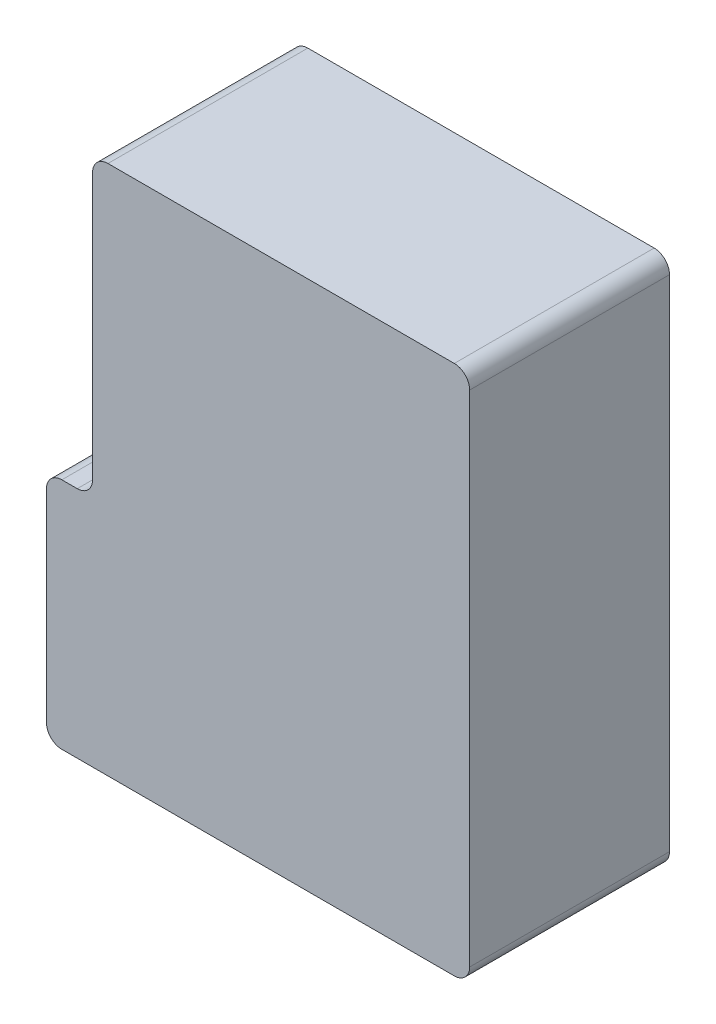
SolidWorks part; units mm, degrees
material "Custom Plastic"
ref_plane "X-Y Datum" through (0, 0, 0) normal (0, 0, 1) x (1, 0, 0)
ref_plane "X-Z Datum" through (0, 0, 0) normal (0, 1, 0) x (1, 0, 0)
ref_plane "Y-Z Datum" through (0, 0, 0) normal (1, 0, 0) x (0, 0, -1)
sketch "Sketch1" plane through (0, 0, 0) normal (0, 0, 1) x (1, 0, 0)
  line L0 (1.8162, 48.1563) -> (125.4513, 48.1563) construction
  line L1 (24.3593, 48.1563) -> (24.3593, 120.2923) construction
  line L3 (24.3593, 120.2923) -> (125.4513, 120.2923) construction
  line L8 (125.4513, 48.1563) -> (125.4513, 120.2923) construction
  line L33 (24.3593, 120.2923) -> (1.8162, 120.2923) construction
  line L34 (24.3593, 120.2923) -> (24.3593, 48.1563) construction
  line L35 (63.6337, 48.1563) -> (63.6337, 43.0763) construction
  line L36 (1.8162, 120.2923) -> (1.8162, 48.1563) construction
  line L41 (24.3593, 120.2923) -> (23.7243, 120.2923) construction
  line L42 (24.3593, 120.2923) -> (24.3593, 122.8323) construction
  line L44 (27.5343, 14.7553) -> (27.5343, 43.0763) construction
  line L45 (125.4513, 120.2923) -> (127.9913, 120.2923) construction
  line L46 (27.5343, 14.7553) -> (125.4513, 14.7553) construction
  line L47 (23.7243, 122.8323) -> (127.9913, 122.8323)
  line L48 (23.7243, 122.8323) -> (23.7243, -21.9477)
  line L49 (23.7243, -21.9477) -> (127.9913, -21.9477)
  line L50 (127.9913, 122.8323) -> (127.9913, -21.9477)
  line L51 (125.4513, 14.7553) -> (125.4513, 43.0763) construction
  line L52 (27.5343, 43.0763) -> (125.4513, 43.0763) construction
  line L53 (23.7243, 120.2923) -> (23.7243, 48.1563) construction
  circle A17 centre (30.4553, 114.1963) radius 2.1 construction
  circle A18 centre (119.8633, 115.2123) radius 2.1 construction
  circle A19 centre (119.6813, 54.2533) radius 2.1 construction
  circle A20 centre (29.4393, 53.2363) radius 2.1 construction
  circle A26 centre (31.9793, 18.4383) radius 2.1 construction
  circle A27 centre (31.9793, 39.3933) radius 2.1 construction
  circle A28 centre (120.6193, 28.8183) radius 2.1 construction
sketch "Sketch2" plane through (0, 0, 0) normal (0, 0, 1) x (1, 0, 0)
  line L4 (55.176, 122.8323) -> (127.9913, 122.8323)
  line L6 (55.176, 48.5244) -> (55.176, 50.9244) construction
  line L7 (55.176, -21.05) -> (127.9913, -21.05)
  line L8 (127.9913, 122.8323) -> (127.9913, -21.05)
  line L9 (55.176, 110.2103) -> (127.9913, -21.05) construction
  line L10 (55.176, -8.428) -> (127.9913, 122.8323) construction
  line L11 (55.176, 50.9244) -> (55.176, -21.05)
  line L12 (55.176, 50.9244) -> (55.176, 122.8323)
  circle A7 centre (88.0827, 6.45) radius 27.5
  circle A8 centre (88.0294, 95.3501) radius 27.5
  circle A9 centre (98.216, 50.8911) radius 6.477
  circle A10 centre (77.896, 50.9089) radius 6.477
  circle A11 centre (121.5143, 31.8208) radius 6.477
  circle A12 centre (115.996, 50.8756) radius 2.4
  circle A13 centre (55.176, 50.9244) radius 2.4
  point P14 (88.0827, 50.8911)
sketch "Sketch3" plane through (0, 0, 0) normal (0, 0, 1) x (1, 0, 0)
  line L0 (119.5956, 120.2923) -> (119.5956, 122.8323) construction
  line L1 (24.3593, 120.2923) -> (125.4513, 120.2923) construction
  line L2 (127.9913, 122.8323) -> (127.9913, 110.1323) construction
  line L3 (127.9913, 122.8323) -> (127.9913, -21.9477) construction
  line L4 (127.9913, 110.1323) -> (130.5313, 110.1323) construction
  line L5 (127.9913, -21.9477) -> (127.9913, -9.2477) construction
  line L6 (127.9913, -9.2477) -> (130.5313, -9.2477) construction
  line L7 (127.9913, 50.4423) -> (130.5313, 50.4423) construction
  line L8 (75.8578, 122.8323) -> (75.8578, -32.9894) construction
  line L9 (23.7243, 122.8323) -> (127.9913, 122.8323) construction
  line L10 (23.7243, 31.0503) -> (21.1843, 31.0503) construction
  line L11 (23.7243, -9.2477) -> (21.1843, -9.2477) construction
  line L12 (23.7243, -21.9477) -> (23.7243, -9.2477) construction
  line L13 (23.7243, 122.8323) -> (23.7243, -21.9477) construction
  line L14 (23.7243, 122.8323) -> (23.7243, 110.1323) construction
  line L15 (32.12, 120.2923) -> (32.12, 122.8323) construction
  line L17 (23.7243, 135.5323) -> (143.2313, 135.5323)
  line L18 (8.4843, 37.4003) -> (8.4843, -34.6477)
  line L19 (8.4843, -34.6477) -> (143.2313, -34.6477)
  line L20 (143.2313, 135.5323) -> (143.2313, -34.6477)
  line L22 (23.7243, 48.1563) -> (23.7243, 135.5323)
  line L23 (8.4843, 37.4003) -> (23.7243, 37.4003)
  line L24 (23.7243, 37.4003) -> (23.7243, 48.1563)
  circle A0 centre (119.5956, 129.1823) radius 6.35 construction
  circle A1 centre (136.8813, 110.1323) radius 6.35 construction
  circle A2 centre (136.8813, -9.2477) radius 6.35 construction
  circle A3 centre (136.8813, 50.4423) radius 6.35 construction
  circle A4 centre (119.5956, -28.2977) radius 6.35 construction
  circle A5 centre (32.12, -28.2977) radius 6.35 construction
  circle A7 centre (14.8343, -9.2477) radius 6.35 construction
  circle A9 centre (32.12, 129.1823) radius 6.35 construction
  circle A10 centre (14.8343, 31.0503) radius 6.35 construction
extrude "Boss-Extrude1" add sketch "Sketch3" along normal blind 63.5
shell "Shell1" thickness 2.54 removed face at (58.48, 46.095, 0) outward yes
sketch "Sketch6" plane through (0, 0, 63.5) normal (0, 0, -1) x (-1, 0, 0)
  line L0 (-125.9456, -28.2977) -> (-125.9456, -34.6477)
  line L1 (-8.4843, -34.6477) -> (-143.2313, -34.6477) construction
  line L2 (-125.9456, -34.6477) -> (-113.2456, -34.6477)
  line L3 (-113.2456, -34.6477) -> (-113.2456, -28.2977)
  line L4 (-136.8813, -2.8977) -> (-143.2313, -2.8977)
  line L5 (-143.2313, 135.5323) -> (-143.2313, -34.6477) construction
  line L6 (-143.2313, -2.8977) -> (-143.2313, -15.5977)
  line L7 (-143.2313, -15.5977) -> (-136.8813, -15.5977)
  line L8 (-38.47, -28.2977) -> (-38.47, -34.6477)
  line L9 (-38.47, -34.6477) -> (-25.77, -34.6477)
  line L10 (-25.77, -34.6477) -> (-25.77, -28.2977)
  line L11 (-14.8343, -2.8977) -> (-8.4843, -2.8977)
  line L12 (-8.4843, 37.4003) -> (-8.4843, -34.6477) construction
  line L13 (-8.4843, -2.8977) -> (-8.4843, -15.5977)
  line L14 (-8.4843, -15.5977) -> (-14.8343, -15.5977)
  line L15 (-14.8343, 24.7003) -> (-8.4843, 24.7003)
  line L16 (-8.4843, 24.7003) -> (-8.4843, 37.4003)
  line L17 (-8.4843, 37.4003) -> (-14.8343, 37.4003)
  line L18 (-136.8813, 56.7923) -> (-143.2313, 56.7923)
  line L19 (-143.2313, 56.7923) -> (-143.2313, 44.0923)
  line L20 (-143.2313, 44.0923) -> (-136.8813, 44.0923)
  line L21 (-136.8813, 116.4823) -> (-143.2313, 116.4823)
  line L22 (-143.2313, 116.4823) -> (-143.2313, 103.7823)
  line L23 (-143.2313, 103.7823) -> (-136.8813, 103.7823)
  line L24 (-125.9456, 129.1823) -> (-125.9456, 135.5323)
  line L25 (-23.7243, 135.5323) -> (-143.2313, 135.5323) construction
  line L26 (-125.9456, 135.5323) -> (-113.2456, 135.5323)
  line L27 (-113.2456, 135.5323) -> (-113.2456, 129.1823)
  line L28 (-38.47, 129.1823) -> (-38.47, 135.5323)
  line L29 (-25.77, 129.1823) -> (-23.7243, 129.1823)
  line L30 (-23.7243, 48.1563) -> (-23.7243, 135.5323) construction
  line L31 (-23.7243, 129.1823) -> (-23.7243, 135.5323)
  line L32 (-23.7243, 135.5323) -> (-38.47, 135.5323)
  line L33 (-75.8578, 122.8323) -> (-75.8578, -32.9894) construction
  line L34 (-82.2078, 129.1823) -> (-82.2078, 135.5323)
  line L35 (-82.2078, 135.5323) -> (-69.5078, 135.5323)
  line L36 (-69.5078, 135.5323) -> (-69.5078, 129.1823)
  line L37 (-82.2078, -28.2977) -> (-82.2078, -34.6477)
  line L38 (-82.2078, -34.6477) -> (-69.5078, -34.6477)
  line L39 (-69.5078, -34.6477) -> (-69.5078, -28.2977)
  arc A0 (-125.9456, 129.1823) -> (-113.2456, 129.1823) centre (-119.5956, 129.1823) ccw
  arc A1 (-38.47, 129.1823) -> (-25.77, 129.1823) centre (-32.12, 129.1823) ccw
  arc A2 (-136.8813, 103.7823) -> (-136.8813, 116.4823) centre (-136.8813, 110.1323) ccw
  arc A3 (-136.8813, 44.0923) -> (-136.8813, 56.7923) centre (-136.8813, 50.4423) ccw
  arc A4 (-136.8813, -15.5977) -> (-136.8813, -2.8977) centre (-136.8813, -9.2477) ccw
  arc A5 (-113.2456, -28.2977) -> (-125.9456, -28.2977) centre (-119.5956, -28.2977) ccw
  arc A6 (-14.8343, -2.8977) -> (-14.8343, -15.5977) centre (-14.8343, -9.2477) ccw
  arc A7 (-14.8343, 37.4003) -> (-14.8343, 24.7003) centre (-14.8343, 31.0503) ccw
  arc A8 (-25.77, -28.2977) -> (-38.47, -28.2977) centre (-32.12, -28.2977) ccw
  arc A9 (-69.5078, -28.2977) -> (-82.2078, -28.2977) centre (-75.8578, -28.2977) ccw
  arc A10 (-82.2078, 129.1823) -> (-69.5078, 129.1823) centre (-75.8578, 129.1823) ccw
extrude "Boss-Extrude2" add sketch "Sketch6" along normal blind 63.5
sketch "Sketch7" plane through (0, 0, 63.5) normal (0, 0, -1) x (-1, 0, 0)
  line L0 (-23.7243, 58.6553) -> (-23.7243, 46.8863) construction
  line L1 (-27.7674, 119.0223) -> (-128.8594, 119.0223) construction
  line L2 (-27.7674, 119.0223) -> (-27.7674, 46.8863) construction
  line L3 (-27.7674, 46.8863) -> (-128.8594, 46.8863) construction
  line L4 (-128.8594, 119.0223) -> (-128.8594, 46.8863) construction
  line L5 (-27.7674, 46.8863) -> (-5.2243, 46.8863) construction
  line L6 (-27.7674, 46.8863) -> (-27.7674, 119.0223) construction
  line L7 (-27.7674, 119.0223) -> (-5.2243, 119.0223) construction
  line L8 (-5.2243, 46.8863) -> (-5.2243, 119.0223) construction
  circle A0 centre (-123.0894, 112.9253) radius 6.35
  circle A1 centre (-32.8474, 113.9423) radius 6.35
  circle A2 centre (-120.6193, 28.8183) radius 6.35
  circle A3 centre (-31.9793, 39.3933) radius 6.35
  circle A4 centre (-31.9793, 18.4383) radius 6.35
  circle A5 centre (-33.8634, 52.9823) radius 6.35
  circle A6 centre (-123.2714, 51.9663) radius 6.35
  circle A7 centre (-33.8634, 52.9823) radius 2.1 construction
  circle A8 centre (-123.2714, 51.9663) radius 2.1 construction
  circle A9 centre (-123.0894, 112.9253) radius 2.1 construction
  circle A10 centre (-32.8474, 113.9423) radius 2.1 construction
extrude "Boss-Extrude3" add sketch "Sketch7" along normal blind 6.27
sketch "Sketch8" plane through (0, 0, 0) normal (0, 0, -1) x (-1, 0, 0)
  line L0 (-75.8578, 122.8323) -> (-75.8578, -32.9894) construction
  circle A0 centre (-119.5956, 129.1823) radius 2.625
  circle A1 centre (-136.8813, 110.1323) radius 2.625
  circle A2 centre (-75.8578, 129.1823) radius 2.625
  circle A3 centre (-32.12, 129.1823) radius 2.625
  circle A4 centre (-136.8813, 50.4423) radius 2.625
  circle A5 centre (-136.8813, -9.2477) radius 2.625
  circle A6 centre (-119.5956, -28.2977) radius 2.625
  circle A7 centre (-75.8578, -28.2977) radius 2.625
  circle A8 centre (-32.12, -28.2977) radius 2.625
  circle A9 centre (-14.8343, -9.2477) radius 2.625
  circle A10 centre (-14.8343, 31.0503) radius 2.625
extrude "Cut-Extrude1" cut sketch "Sketch8" against normal blind 10
fillet "Fillet1" radius 5.08 11 edges at (21.1843, 138.0723, 33.02) (145.7713, 138.0723, 33.02) (145.7713, -37.1877, 33.02) (5.9443, -37.1877, 33.02) (5.9443, 39.9403, 33.02) (21.1843, 39.9403, 33.02) (23.7243, 129.1823, 31.75) (143.2313, 135.5323, 31.75) (143.2313, -34.6477, 31.75) (8.4843, -34.6477, 31.75) (23.7243, 37.4003, 31.75)
fillet "Fillet2" radius 2 21 edges at (69.5078, -34.6477, 31.75) (82.2078, -34.6477, 31.75) (113.2456, -34.6477, 31.75) (125.9456, -34.6477, 31.75) (143.2313, -15.5977, 31.75) (143.2313, -2.8977, 31.75) (143.2313, 44.0923, 31.75) (143.2313, 56.7923, 31.75) (143.2313, 103.7823, 31.75) (143.2313, 116.4823, 31.75) (113.2456, 135.5323, 31.75) (125.9456, 135.5323, 31.75) (82.2078, 135.5323, 31.75) (69.5078, 135.5323, 31.75) (38.47, 135.5323, 31.75) (14.8343, 37.4003, 31.75) (8.4843, 24.7003, 31.75) (8.4843, -15.5977, 31.75) (8.4843, -2.8977, 31.75) (38.47, -34.6477, 31.75) (25.77, -34.6477, 31.75)
sketch "Sketch9" plane through (0, 0, 57.23) normal (0, 0, -1) x (-1, 0, 0)
  circle A0 centre (-123.0894, 112.9253) radius 2.625
  circle A1 centre (-32.8474, 113.9423) radius 2.625
  circle A2 centre (-123.2714, 51.9663) radius 2.625
  circle A3 centre (-33.8634, 52.9823) radius 2.625
  circle A4 centre (-31.9793, 39.3933) radius 2.625
  circle A5 centre (-31.9793, 18.4383) radius 2.625
  circle A6 centre (-120.6193, 28.8183) radius 2.625
  point P2 (-123.2714, 51.9663)
  point P5 (-123.0894, 112.9253)
  point P8 (-32.8474, 113.9423)
  point P11 (-33.8634, 52.9823)
extrude "Cut-Extrude2" cut sketch "Sketch9" against normal blind 6.27
sketch "Sketch10" plane through (0, 0, 63.5) normal (0, 0, -1) x (-1, 0, 0)
  line L0 (-23.7243, 122.8323) -> (-23.7243, -21.9477) construction
  line L1 (-23.7243, 46.8863) -> (-143.2313, 46.8863)
  line L2 (-23.7243, 46.8863) -> (-23.7243, 45.7433)
  line L3 (-23.7243, 45.7433) -> (-143.2313, 45.7433)
  line L4 (-143.2313, 46.8863) -> (-143.2313, 45.7433)
  line L5 (-143.2313, 135.5323) -> (-143.2313, -34.6477) construction
sketch "Sketch11" plane through (0, 0, 0) normal (0, 0, -1) x (-1, 0, 0)
  line L0 (-11.0243, 39.9403) -> (-16.1043, 39.9403)
  line L1 (-140.6913, 138.0723) -> (-26.2643, 138.0723)
  line L2 (-145.7713, 132.9923) -> (-145.7713, -32.1077)
  line L3 (-140.6913, -37.1877) -> (-11.0243, -37.1877)
  line L4 (-5.9443, 34.8603) -> (-5.9443, -32.1077)
  line L5 (-21.1843, 45.0203) -> (-21.1843, 132.9923)
  arc A0 (-145.7713, -32.1077) -> (-140.6913, -37.1877) centre (-140.6913, -32.1077) ccw
  arc A1 (-11.0243, -37.1877) -> (-5.9443, -32.1077) centre (-11.0243, -32.1077) ccw
  arc A2 (-11.0243, 39.9403) -> (-5.9443, 34.8603) centre (-11.0243, 34.8603) cw
  arc A3 (-16.1043, 39.9403) -> (-21.1843, 45.0203) centre (-16.1043, 45.0203) cw
  arc A4 (-21.1843, 132.9923) -> (-26.2643, 138.0723) centre (-26.2643, 132.9923) ccw
  arc A5 (-140.6913, 138.0723) -> (-145.7713, 132.9923) centre (-140.6913, 132.9923) ccw
  circle A6 centre (-98.216, 50.8911) radius 6.477
  circle A7 centre (-77.896, 50.9089) radius 6.477
  circle A8 centre (-55.176, 50.9244) radius 2.4
  circle A9 centre (-115.996, 50.8756) radius 2.4
  circle A10 centre (-121.5143, 31.8208) radius 6.477
  circle A11 centre (-88.0294, 95.3501) radius 10
  circle A12 centre (-99.9209, 109.5219) radius 4.5
  circle A13 centre (-76.0119, 81.2843) radius 4.5
  circle A14 centre (-88.0827, 6.45) radius 10
  circle A15 centre (-99.9743, 20.6218) radius 4.5
  circle A16 centre (-76.0653, -7.6158) radius 4.5
  circle A17 centre (-119.5956, 129.1823) radius 2
  circle A18 centre (-75.8578, 129.1823) radius 2
  circle A19 centre (-32.12, 129.1823) radius 2
  circle A20 centre (-136.8813, 110.1323) radius 2
  circle A21 centre (-32.8474, 113.9423) radius 2
  circle A22 centre (-136.8813, 50.4423) radius 2
  circle A23 centre (-136.8813, -9.2477) radius 2
  circle A24 centre (-119.5956, -28.2977) radius 2
  circle A25 centre (-75.8578, -28.2977) radius 2
  circle A26 centre (-32.12, -28.2977) radius 2
  circle A27 centre (-14.8343, -9.2477) radius 2
  circle A28 centre (-14.8343, 31.0503) radius 2
  point P40 (-88.0294, 95.3501)
  point P41 (-88.0827, 6.45)
  dimension "D1" = 5.08
sketch "Sketch12" plane through (21.1843, 0, 0) normal (-1, 0, 0) x (0, 0, 1)
  line L0 (58.1828, 72.5513) -> (58.1828, 83.7593)
  line L1 (57.9288, 66.4553) -> (34.3288, 66.4553) construction
  line L2 (57.9288, 66.4553) -> (57.9288, 89.8553) construction
  line L3 (57.9288, 89.8553) -> (34.3288, 89.8553) construction
  line L4 (34.3288, 66.4553) -> (34.3288, 89.8553) construction
  line L5 (51.8328, 90.1093) -> (40.4248, 90.1093)
  line L6 (34.0748, 72.5513) -> (34.0748, 72.6139)
  line L7 (51.8328, 66.2013) -> (40.4248, 66.2013)
  line L8 (35.3128, 73.6553) -> (32.3288, 73.6553) construction
  line L9 (35.3128, 73.6553) -> (35.3128, 82.6553) construction
  line L10 (35.3128, 82.6553) -> (32.3288, 82.6553) construction
  line L11 (32.3288, 73.6553) -> (32.3288, 82.6553) construction
  line L12 (35.3128, 73.6553) -> (32.3288, 82.6553) construction
  line L13 (35.3128, 82.6553) -> (32.3288, 73.6553) construction
  line L14 (31.7954, 74.3919) -> (31.7954, 81.9187)
  line L15 (33.5668, 73.1219) -> (33.0654, 73.1219)
  line L16 (34.0748, 83.6967) -> (34.0748, 83.7593)
  line L17 (33.5668, 83.1887) -> (33.0654, 83.1887)
  line L18 (66.04, 132.9923) -> (0, 132.9923) construction
  line L19 (66.04, 132.9923) -> (66.04, 45.0203) construction
  line L20 (66.04, 45.0203) -> (0, 45.0203) construction
  line L21 (0, 132.9923) -> (0, 45.0203) construction
  circle A0 centre (35.3288, 64.4553) radius 1.085
  circle A1 centre (35.3288, 91.8553) radius 1.085
  circle A2 centre (53.4288, 62.9553) radius 1.085
  circle A3 centre (53.4288, 93.3553) radius 1.085
  arc A4 (58.1828, 83.7593) -> (51.8328, 90.1093) centre (51.8328, 83.7593) ccw
  arc A5 (58.1828, 72.5513) -> (51.8328, 66.2013) centre (51.8328, 72.5513) cw
  arc A6 (40.4248, 90.1093) -> (34.0748, 83.7593) centre (40.4248, 83.7593) ccw
  arc A7 (34.0748, 72.5513) -> (40.4248, 66.2013) centre (40.4248, 72.5513) ccw
  arc A8 (33.0654, 83.1887) -> (31.7954, 81.9187) centre (33.0654, 81.9187) ccw
  arc A9 (31.7954, 74.3919) -> (33.0654, 73.1219) centre (33.0654, 74.3919) ccw
  arc A10 (34.0748, 83.6967) -> (33.5668, 83.1887) centre (33.5668, 83.6967) cw
  arc A11 (34.0748, 72.6139) -> (33.5668, 73.1219) centre (33.5668, 72.6139) ccw
  point P8 (46.1288, 78.1553)
  point P13 (33.8208, 78.1553)
  point P46 (66.04, 132.9923)
extrude "Cut-Extrude3" cut sketch "Sketch12" against normal blind 2.54
